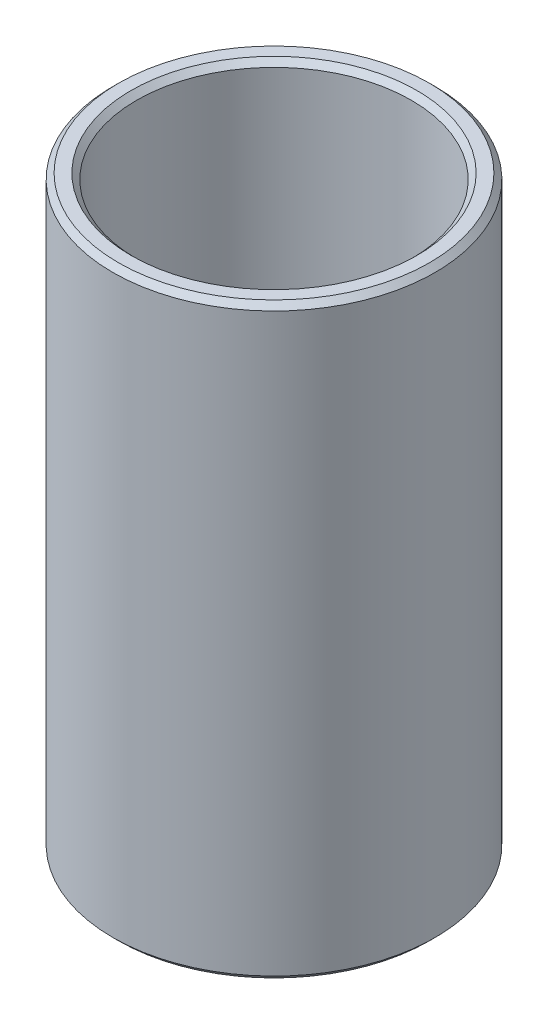
SolidWorks part; units mm, degrees
ref_plane "Front Plane" through (0, 0, 0) normal (0, 0, 1) x (1, 0, 0)
ref_plane "Top Plane" through (0, 0, 0) normal (0, 1, 0) x (1, 0, 0)
ref_plane "Right Plane" through (0, 0, 0) normal (1, 0, 0) x (0, 0, -1)
sketch "Sketch1" plane through (0, 0, 0) normal (0, 1, 0) x (1, 0, 0)
  circle A0 centre (0, 0) radius 35
  dimension "SLEEVE_OD" = 70
extrude "Boss-Extrude1" add sketch "Sketch1" along normal blind 127.5422
sketch "Sketch2" plane through (0, 0, 0) normal (0, 1, 0) x (1, 0, 0)
  circle A0 centre (0, 0) radius 29.8279
  dimension "BORE_D" = 59.6558
extrude "Cut-Extrude1" cut sketch "Sketch2" along normal through all
chamfer "Chamfer1" distance 1.2205 angle 45 4 edges at (0, 127.5422, 29.8279) (0, 0, 29.8279) (0, 0, 35) (0, 127.5422, 35)
